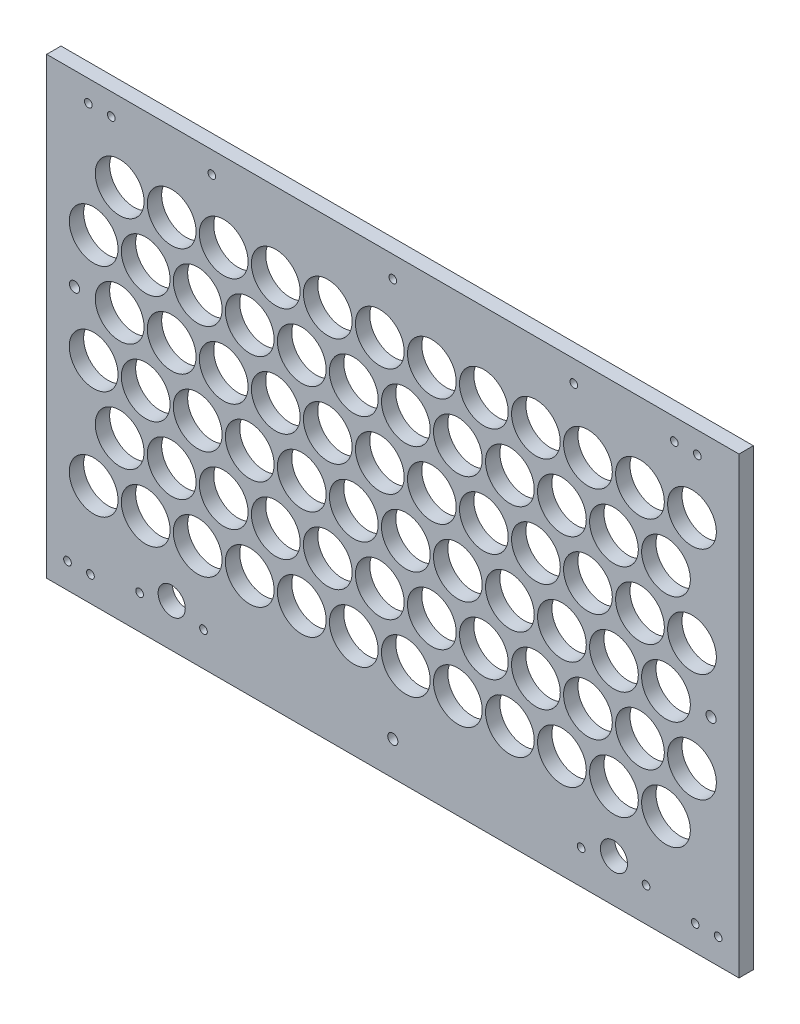
SolidWorks part; units mm, degrees
material "ABS"
ref_plane "X-Y Datum" through (0, 0, 0) normal (0, 0, 1) x (1, 0, 0)
ref_plane "X-Z Datum" through (0, 0, 0) normal (0, 1, 0) x (1, 0, 0)
ref_plane "Y-Z Datum" through (0, 0, 0) normal (1, 0, 0) x (0, 0, -1)
sketch "Sketch1" plane through (0, 0, 0) normal (0, 0, 1) x (1, 0, 0)
  line L1 (-143.025, 70.775) -> (143.025, 70.775)
  line L2 (-143.025, 70.775) -> (-143.025, -70.775)
  line L3 (-143.025, -70.775) -> (143.025, -70.775)
  line L4 (143.025, 70.775) -> (143.025, -70.775)
  line L5 (-143.025, 70.775) -> (143.025, -70.775) construction
  line L6 (-143.025, -70.775) -> (143.025, 70.775) construction
  line L13 (-153.025, -105.775) -> (153.025, -105.775)
  line L14 (-153.025, 91.65) -> (153.025, 91.65)
  line L15 (-153.025, 91.65) -> (-153.025, -105.775)
  line L16 (153.025, 91.65) -> (153.025, -105.775)
  line L17 (153.025, 70.775) -> (153.025, -70.775) construction
  line L18 (-143.025, 91.65) -> (143.025, 91.65) construction
  line L19 (-143.025, -105.775) -> (143.025, -105.775) construction
  line L20 (-153.025, 70.775) -> (-153.025, -70.775) construction
  line L21 (-132.25, -60) -> (-109.25, -60) construction
  circle A0 centre (-132.25, -60) radius 10.775
  circle A1 centre (-109.25, -60) radius 10.775 construction
  circle A2 centre (-120.75, -36) radius 10.775
  point P0 (0, 0)
  point P16 (-120.75, -60)
  dimension "D1" = 21.55
  dimension "D2" = 23
  dimension "D3" = 24
  dimension "D5" = 141.55
  dimension "D6" = 286.05
  dimension "D7" = 35
  dimension "D8" = 20.875
  dimension "D9" = 10
  dimension "D10" = 10
extrude "Boss-Extrude1" add sketch "Sketch1" along normal blind 6.35 contours A0 L3 L4 L1 L2 A2 | A2 | A0 | A0 L2 L3 | L1 L4 L3 L2 region at (2.4105, 0.9241, 0) region at (-140.6182, -68.3682, 0) region at (-132.25, -60, 0) region at (-149.383, -7.0625, 0) region at (-120.75, -36, 0)
sketch "Sketch3" plane through (0, 0, 6.35) normal (0, 0, 1) x (1, 0, 0)
  line L4 (143.025, 70.775) -> (-143.025, 70.775)
  line L5 (143.025, -70.775) -> (143.025, 70.775)
  line L6 (-143.025, -70.775) -> (143.025, -70.775)
  line L7 (-143.025, 70.775) -> (-143.025, -70.775)
  line L8 (143.025, 70.775) -> (-143.025, 70.775)
  line L9 (143.025, -70.775) -> (143.025, 70.775)
  line L10 (-143.025, -70.775) -> (143.025, -70.775)
  line L11 (-143.025, 70.775) -> (-143.025, -70.775)
  circle A1 centre (-120.75, -36) radius 10.775
  circle A2 centre (-120.75, -36) radius 10.775
  circle A3 centre (-132.25, -60) radius 10.775
  circle A4 centre (-132.25, -60) radius 10.775
  dimension "D1" = 0
  dimension "D2" = 0
  dimension "D3" = 0
extrude "Cut-Extrude1" cut sketch "Sketch3" against normal through all contours A4 region at (-132.25, -60, 6.35)
sketch "Sketch4" plane through (0, 0, 6.35) normal (0, 0, 1) x (1, 0, 0)
  line L4 (143.025, 70.775) -> (-143.025, 70.775)
  line L5 (143.025, -70.775) -> (143.025, 70.775)
  line L6 (-143.025, -70.775) -> (143.025, -70.775)
  line L7 (-143.025, 70.775) -> (-143.025, -70.775)
  line L8 (143.025, 70.775) -> (-143.025, 70.775)
  line L9 (143.025, -70.775) -> (143.025, 70.775)
  line L10 (-143.025, -70.775) -> (143.025, -70.775)
  line L11 (-143.025, 70.775) -> (-143.025, -70.775)
  circle A1 centre (-120.75, -36) radius 10.775
  circle A2 centre (-120.75, -36) radius 10.775
  circle A3 centre (-132.25, -60) radius 10.775
  circle A4 centre (-132.25, -60) radius 10.775
  dimension "D1" = 0
  dimension "D2" = 0
  dimension "D3" = 0
extrude "Cut-Extrude2" cut sketch "Sketch4" against normal through all contours A2 region at (-120.75, -36, 6.35)
pattern_linear "LPattern1" count 12 spacing 23 along (1, 0, 0) of "Cut-Extrude1", "Cut-Extrude2"
pattern_linear "LPattern2" count 3 spacing 48 along (0, 1, 0) of "LPattern1"
sketch "Sketch5" plane through (0, 0, 0) normal (0, 0, -1) x (-1, 0, 0)
sketch "Sketch13" plane through (0, 91.65, 0) normal (0, 1, 0) x (1, 0, 0)
  line L4 (153.025, 0) -> (-153.025, 0)
  line L5 (-153.025, 0) -> (-153.025, -6.35)
  line L6 (-153.025, -6.35) -> (153.025, -6.35)
  line L7 (153.025, -6.35) -> (153.025, 0)
  line L8 (153.025, 0) -> (-153.025, 0)
  line L9 (-153.025, 0) -> (-153.025, -6.35)
  line L10 (-153.025, -6.35) -> (153.025, -6.35)
  line L11 (153.025, -6.35) -> (153.025, 0)
  dimension "D1" = 0
extrude "Boss-Extrude2" add sketch "Sketch13" along normal blind 3.175
sketch "Sketch14" plane through (0, 0, 0) normal (0, 0, -1) x (-1, 0, 0)
  circle A0 centre (-97.75, -86.775) radius 6
extrude "Cut-Extrude3" cut sketch "Sketch14" against normal through all
mirror "Mirror1" about plane through (0, 0, 0) normal (1, 0, 0) of "Cut-Extrude3"
sketch "Sketch15" plane through (0, 0, 0) normal (0, 0, -1) x (-1, 0, 0)
  point P0 (-111.94, -90.775)
  point P1 (-83.25, -90.775)
  point P3 (83.712, -90.775)
  point P5 (111.94, -90.775)
  point P7 (134.61, 85.3)
  point P9 (124.45, 85.3)
  point P11 (80, 85.3)
  point P13 (0, 85.3)
  point P15 (-80, 85.3)
  point P17 (-124.45, 85.3)
  point P19 (-134.61, 85.3)
  point P25 (143.8175, -94.6)
  point P27 (133.6575, -94.6)
  point P29 (-133.6575, -94.6)
  point P31 (-143.8175, -94.6)
hole_wizard "M3 Clearance Hole1" positions "Sketch15" profile "Sketch16" hole size "M3" standard "ANSI Metric" end condition through all
sketch "Sketch16" plane through (111.94, -90.775, 0) normal (1, 0, 0) x (0, 1, 0)
  line L0 (0, 0) -> (0, 6.35)
  line L1 (0, 6.35) -> (1.7, 6.35)
  line L2 (1.7, 6.35) -> (1.7, 0)
  line L5 (1.7, 0) -> (0, 0)
  line L11 (0, -6.35) -> (0, 107.95) construction
  dimension "Thru Hole Dia." = 3.4
  dimension "Thru Hole Depth" = 6.35
sketch "Sketch17" plane through (0, 0, 0) normal (0, 0, -1) x (-1, 0, 0)
  line L0 (0, -105.775) -> (0, -77.9164) construction
  line L1 (153.025, -105.775) -> (-153.025, -105.775) construction
  circle A0 centre (0, -90.775) radius 2.25
  circle A1 centre (140.6875, 12) radius 2.25
  circle A2 centre (-140.6875, -12) radius 2.25
  point P0 (-140.6875, -12)
  point P1 (140.6875, 12)
  point P9 (0, -90.775)
  point P11 (83.712, -90.775)
  dimension "D1" = 4.5
extrude "Cut-Extrude4" cut sketch "Sketch17" against normal through all
